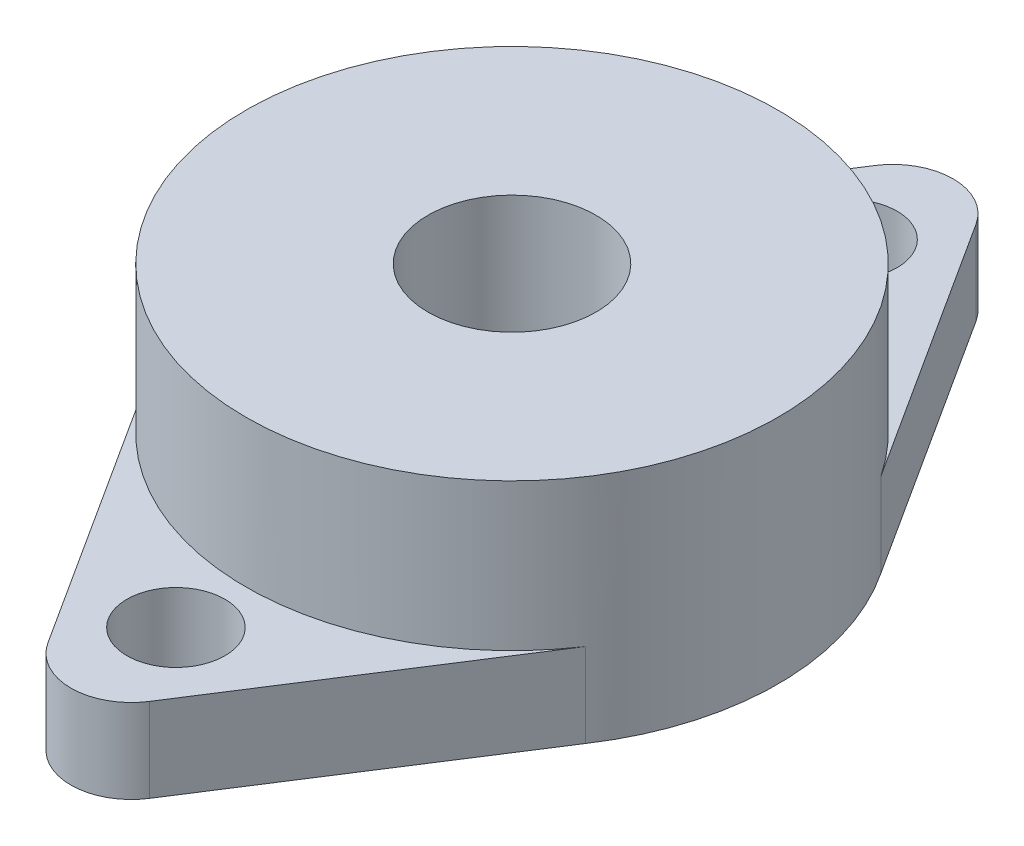
SolidWorks part; units mm, degrees
ref_plane "Front Plane" through (0, 0, 0) normal (0, 0, 1) x (1, 0, 0)
ref_plane "Top Plane" through (0, 0, 0) normal (0, 1, 0) x (1, 0, 0)
ref_plane "Right Plane" through (0, 0, 0) normal (1, 0, 0) x (0, 0, -1)
sketch "Sketch1" plane through (0, 0, 0) normal (0, 1, 0) x (1, 0, 0)
  circle A0 centre (0, 0) radius 19
  dimension "D1" = 38
extrude "Boss-Extrude1" add sketch "Sketch1" along normal blind 16.5
sketch "Sketch2" plane through (0, 0, 0) normal (0, 1, 0) x (1, 0, 0)
  line L0 (0, 31.5) -> (0, -31.5) construction
  line L4 (-15.8019, 10.5498) -> (-3.6195, 29.5227)
  line L5 (15.8019, 10.5498) -> (3.6195, 29.5227)
  line L6 (-15.8019, 10.5498) -> (15.8019, 10.5498)
  circle A1 centre (0, 0) radius 19 construction
  circle A2 centre (0, 27.1986) radius 4.3014
  point P5 (0, 0)
  point P8 (0, 31.5)
  dimension "D1" = 63
extrude "Boss-Extrude2" add sketch "Sketch2" along normal blind 6 contours L0 A2 L4 L6 | A2 L0 L6 L5 | A2 L0 | L0 A2 region at (1.8256, 0, -27.1986) region at (-1.8256, 0, -27.1986) region at (6.0287, 0, -16.7804) region at (-6.0287, 0, -16.7804)
sketch "Sketch3" plane through (0, 16.5, 0) normal (0, 1, 0) x (1, 0, 0)
  circle A0 centre (0, 0) radius 6
  dimension "D1" = 12
extrude "Cut-Extrude1" cut sketch "Sketch3" against normal through all
sketch "Sketch4" plane through (0, 6, 0) normal (0, 1, 0) x (1, 0, 0)
  line L0 (0, 31.5) -> (0, 0) construction
  arc A0 (3.6195, 29.5227) -> (-3.6195, 29.5227) centre (0, 27.1986) ccw construction
  circle A1 centre (0, 24) radius 3.5
  circle A3 centre (0, 0) radius 19 construction
  dimension "D1" = 24
  dimension "D2" = 7
extrude "Cut-Extrude2" cut sketch "Sketch4" against normal through all
mirror "Mirror1" about plane through (0, 0, 0) normal (0, 0, 1) of "Cut-Extrude2", "Boss-Extrude2"
